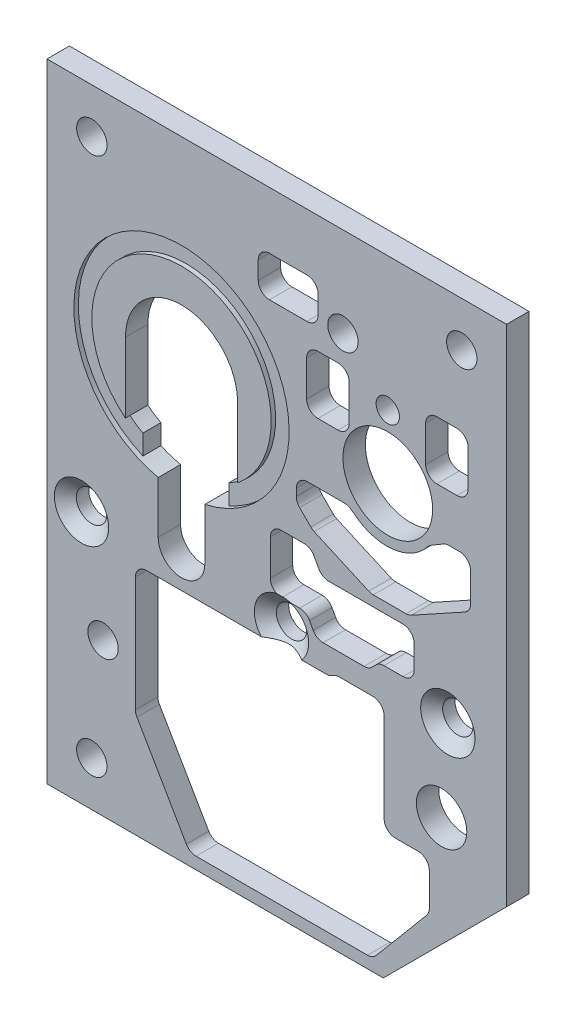
SolidWorks part; units mm, degrees
material "Acrylic (Medium-high impact)"
ref_plane "Front Plane" through (0, 0, 0) normal (0, 0, 1) x (1, 0, 0)
ref_plane "Top Plane" through (0, 0, 0) normal (0, 1, 0) x (1, 0, 0)
ref_plane "Right Plane" through (0, 0, 0) normal (1, 0, 0) x (0, 0, -1)
sketch "Sketch1" plane through (0, 0, 0) normal (0, 0, 1) x (1, 0, 0)
  line L5 (-65.0875, 0) -> (-65.0875, -88.9)
  line L6 (-65.0875, -88.9) -> (-17.4625, -88.9)
  line L7 (-17.4625, -88.9) -> (0, -71.4375)
  line L8 (0, -71.4375) -> (0, 0)
  line L9 (0, 0) -> (-65.0875, 0)
  line L10 (-65.0875, 0) -> (-65.0875, -88.9)
  line L11 (-65.0875, -88.9) -> (-17.4625, -88.9)
  line L12 (-17.4625, -88.9) -> (0, -71.4375)
  line L13 (0, -71.4375) -> (0, 0)
  line L14 (0, 0) -> (-65.0875, 0)
  dimension "D1" = 0
extrude "Boss-Extrude1" add sketch "Sketch1" against normal blind 3.175
hole_wizard "#6 Clearance Hole1" positions "Sketch3" profile "Sketch2" hole size "#6" standard "ANSI Inch" end condition through all
sketch "Sketch3" plane through (0, 0, 0) normal (0, 0, 1) x (1, 0, 0)
  point P0 (-58.7375, -6.35)
  point P3 (-6.35, -6.35)
  point P6 (-23.1775, -12.7)
  point P9 (-57.15, -67.31)
  point P12 (-58.7375, -82.55)
sketch "Sketch2" plane through (-58.7375, -6.35, 0) normal (1, 0, 0) x (0, -1, 0)
  line L0 (0, 0) -> (0, 3.175)
  line L1 (0, 3.175) -> (2.1526, 3.175)
  line L2 (2.1526, 3.175) -> (2.1526, 0)
  line L5 (2.1526, 0) -> (0, 0)
  line L11 (0, -6.35) -> (0, 107.95) construction
  dimension "Thru Hole Dia." = 4.3053
  dimension "Thru Hole Depth" = 3.175
sketch "Sketch4" plane through (0, 0, 0) normal (0, 0, 1) x (1, 0, 0)
  line L0 (-49.3395, -50.8) -> (-49.3395, -43.453) construction
  line L1 (-42.7355, -43.453) -> (-42.7355, -50.8) construction
  line L2 (-49.3395, -50.8) -> (-49.3395, -43.453)
  line L3 (-42.7355, -43.453) -> (-42.7355, -50.8)
  arc A0 (-42.7355, -43.453) -> (-49.3395, -43.453) centre (-46.0375, -28.575) ccw construction
  arc A1 (-49.3395, -50.8) -> (-42.7355, -50.8) centre (-46.0375, -50.8) ccw construction
  arc A2 (-42.7355, -43.453) -> (-49.3395, -43.453) centre (-46.0375, -28.575) ccw
  arc A3 (-49.3395, -50.8) -> (-42.7355, -50.8) centre (-46.0375, -50.8) ccw
extrude "Cut-Extrude1" cut sketch "Sketch4" against normal through all
sketch "Sketch5" plane through (0, 0, 0) normal (0, 0, 1) x (1, 0, 0)
  circle A0 centre (-16.8275, -27.94) radius 6.35
  circle A1 centre (-16.8275, -18.9484) radius 1.651
  dimension "D1" = 12.7
  dimension "D2" = 3.302
  dimension "D3" = 8.9916
extrude "Cut-Extrude2" cut sketch "Sketch5" against normal through all
hole_wizard "1/4 Clearance Hole1" positions "Sketch7" profile "Sketch6" hole size "1/4" standard "ANSI Inch" end condition through all
sketch "Sketch7" plane through (0, 0, 0) normal (0, 0, 1) x (1, 0, 0)
  point P0 (-9.2075, -65.0875)
sketch "Sketch6" plane through (-9.2075, -65.0875, 0) normal (1, 0, 0) x (0, -1, 0)
  line L0 (0, 0) -> (0, 3.175)
  line L1 (0, 3.175) -> (3.5712, 3.175)
  line L2 (3.5712, 3.175) -> (3.5712, 0)
  line L5 (3.5712, 0) -> (0, 0)
  line L11 (0, -6.35) -> (0, 107.95) construction
  dimension "Thru Hole Dia." = 7.1425
  dimension "Thru Hole Depth" = 3.175
sketch "Sketch8" plane through (0, 0, -3.175) normal (0, 0, -1) x (-1, 0, 0)
  line L0 (52.1335, -39.7163) -> (52.1335, -42.5427) construction
  line L1 (53.975, -28.575) -> (53.975, -38.4889) construction
  line L2 (38.1, -38.4889) -> (38.1, -28.575) construction
  line L3 (39.9415, -42.5427) -> (39.9415, -39.7163) construction
  line L4 (52.1335, -39.7163) -> (52.1335, -42.5427)
  line L5 (53.975, -28.575) -> (53.975, -38.4889)
  line L6 (38.1, -38.4889) -> (38.1, -28.575)
  line L7 (39.9415, -42.5427) -> (39.9415, -39.7163)
  arc A0 (52.1335, -39.7163) -> (53.975, -38.4889) centre (46.0375, -28.575) ccw construction
  arc A1 (53.975, -28.575) -> (38.1, -28.575) centre (46.0375, -28.575) ccw construction
  arc A2 (38.1, -38.4889) -> (39.9415, -39.7163) centre (46.0375, -28.575) ccw construction
  arc A3 (49.3395, -43.453) -> (42.7355, -43.453) centre (46.0375, -28.575) ccw construction
  arc A4 (52.1335, -39.7163) -> (53.975, -38.4889) centre (46.0375, -28.575) ccw
  arc A5 (53.975, -28.575) -> (38.1, -28.575) centre (46.0375, -28.575) ccw
  arc A6 (38.1, -38.4889) -> (39.9415, -39.7163) centre (46.0375, -28.575) ccw
  arc A7 (52.1335, -42.5427) -> (39.9415, -42.5427) centre (46.0375, -28.575) ccw
extrude "Boss-Extrude2" add sketch "Sketch8" against normal through all
sketch "Sketch9" plane through (0, 0, 0) normal (0, 0, 1) x (1, 0, 0)
  line L0 (-52.1335, -39.7163) -> (-52.1335, -42.5427) construction
  line L1 (-39.9415, -42.5427) -> (-39.9415, -39.7163) construction
  line L2 (-52.1335, -39.7163) -> (-52.1335, -42.5427)
  line L3 (-39.9415, -42.5427) -> (-39.9415, -39.7163)
  arc A0 (-42.7355, -43.453) -> (-49.3395, -43.453) centre (-46.0375, -28.575) ccw construction
  arc A1 (-53.975, -38.4889) -> (-52.1335, -39.7163) centre (-46.0375, -28.575) ccw construction
  arc A2 (-38.1, -38.4889) -> (-53.975, -38.4889) centre (-46.0375, -28.575) ccw construction
  arc A3 (-39.9415, -39.7163) -> (-38.1, -38.4889) centre (-46.0375, -28.575) ccw construction
  arc A4 (-39.9415, -42.5427) -> (-52.1335, -42.5427) centre (-46.0375, -28.575) ccw
  arc A5 (-53.975, -38.4889) -> (-52.1335, -39.7163) centre (-46.0375, -28.575) ccw
  arc A6 (-38.1, -38.4889) -> (-53.975, -38.4889) centre (-46.0375, -28.575) ccw
  arc A7 (-39.9415, -39.7163) -> (-38.1, -38.4889) centre (-46.0375, -28.575) ccw
extrude "Cut-Extrude3" cut sketch "Sketch9" against normal blind 0.635
hole_wizard "CSK for #6 Flat Head Machine Screw (100)1" positions "Sketch11" profile "Sketch10" countersink size "#6" standard "ANSI Inch" end condition through all
sketch "Sketch11" plane through (0, 0, 0) normal (0, 0, 1) x (1, 0, 0)
  point P1 (-31.877, -53.0919)
  point P5 (-60.198, -53.0919)
  point P8 (-8.321, -53.0919)
sketch "Sketch10" plane through (-31.877, -53.0919, 0) normal (1, 0, 0) x (0, -1, 0)
  line L0 (0, 0) -> (0, 3.175)
  line L1 (0, 3.175) -> (2.1526, 3.175)
  line L2 (2.1526, 3.175) -> (2.1526, 1.4209)
  line L3 (2.1526, 1.4209) -> (3.846, 0)
  line L5 (3.846, 0) -> (0, 0)
  line L6 (-2.1526, 1.4209) -> (-3.846, 0) construction
  line L11 (0, -6.35) -> (0, 107.95) construction
  dimension "Thru Hole Dia." = 4.3053
  dimension "Thru Hole Depth" = 3.175
  dimension "Near C'Sink Dia." = 7.692
  dimension "Near C'Sink Angle" = 100
sketch "Sketch13" plane through (0, 0, 0) normal (0, 0, 1) x (1, 0, 0)
  line L0 (-33.5834, -8.0877) -> (-28.2715, -8.0877)
  line L1 (-26.684, -9.6752) -> (-26.684, -12.1963)
  line L2 (-28.2715, -13.7838) -> (-33.5834, -13.7838)
  line L3 (-35.1709, -9.6752) -> (-35.1709, -12.1963)
  line L4 (-9.8743, -16.2715) -> (-7.0294, -16.2715)
  line L5 (-5.4419, -17.859) -> (-5.4419, -22.9231)
  line L6 (-7.0294, -24.5106) -> (-9.8743, -24.5106)
  line L7 (-11.4618, -22.9231) -> (-11.4618, -17.859)
  line L8 (-26.728, -16.6728) -> (-23.8831, -16.6728)
  line L9 (-22.2956, -18.2603) -> (-22.2956, -23.3243)
  line L10 (-23.8831, -24.9118) -> (-26.728, -24.9118)
  line L11 (-28.3155, -23.3243) -> (-28.3155, -18.2603)
  line L17 (-13.0908, -45.6924) -> (-13.0908, -48.9531)
  line L23 (-33.4611, -47.8684) -> (-33.4611, -42.8044)
  line L24 (-29.3162, -37.1302) -> (-27.7292, -38.7172)
  line L25 (-27.2516, -39.0452) -> (-19.5276, -42.4798)
  line L26 (-18.8826, -42.6167) -> (-14.2496, -42.6167)
  line L27 (-13.4825, -42.4191) -> (-5.915, -38.243)
  line L28 (-5.0945, -36.8531) -> (-5.0945, -32.7951)
  line L29 (-6.682, -31.2076) -> (-8.167, -31.2076)
  line L32 (-22.9356, -33.4058) -> (-28.1937, -33.4058)
  line L33 (-29.7812, -34.9933) -> (-29.7812, -36.0077)
  line L34 (-50.973, -55.6802) -> (-25.5623, -55.6802)
  line L37 (-15.7595, -70.8877) -> (-12.5337, -70.8876)
  line L38 (-10.9462, -72.4751) -> (-10.9462, -77.1078)
  line L39 (-11.3183, -78.129) -> (-18.4811, -86.653)
  line L40 (-19.6965, -87.2192) -> (-43.9811, -87.2192)
  line L41 (-45.3548, -86.4273) -> (-52.3467, -74.3556)
  line L42 (-52.5605, -73.56) -> (-52.5605, -57.2677)
  line L43 (-14.6783, -44.1049) -> (-25.206, -44.1049)
  line L44 (-26.5981, -43.2804) -> (-27.2773, -42.0413)
  line L45 (-28.6694, -41.2169) -> (-31.8736, -41.2169)
  line L48 (-25.9975, -52.0435) -> (-20.1851, -52.0435)
  line L49 (-19.0626, -51.5785) -> (-18.4896, -51.0056)
  line L50 (-17.3671, -50.5406) -> (-14.6783, -50.5406)
  line L51 (-27.3896, -51.219) -> (-27.9041, -50.2804)
  line L52 (-29.2962, -49.4559) -> (-31.8736, -49.4559)
  line L54 (-24.662, -55.4002) -> (-24.6221, -55.3728)
  line L55 (-23.7218, -55.0928) -> (-18.9345, -55.0928)
  line L57 (-17.347, -56.6803) -> (-17.347, -69.3002)
  line L58 (-8.9781, -31.4305) -> (-10.7271, -32.4701)
  arc A0 (-28.2715, -8.0877) -> (-26.684, -9.6752) centre (-28.2715, -9.6752) cw
  arc A1 (-26.684, -12.1963) -> (-28.2715, -13.7838) centre (-28.2715, -12.1963) cw
  arc A2 (-33.5834, -13.7838) -> (-35.1709, -12.1963) centre (-33.5834, -12.1963) cw
  arc A3 (-33.5834, -8.0877) -> (-35.1709, -9.6752) centre (-33.5834, -9.6752) ccw
  arc A4 (-5.4419, -22.9231) -> (-7.0294, -24.5106) centre (-7.0294, -22.9231) cw
  arc A5 (-9.8743, -24.5106) -> (-11.4618, -22.9231) centre (-9.8743, -22.9231) cw
  arc A6 (-9.8743, -16.2715) -> (-11.4618, -17.859) centre (-9.8743, -17.859) ccw
  arc A7 (-7.0294, -16.2715) -> (-5.4419, -17.859) centre (-7.0294, -17.859) cw
  arc A8 (-22.2956, -23.3243) -> (-23.8831, -24.9118) centre (-23.8831, -23.3243) cw
  arc A9 (-26.728, -24.9118) -> (-28.3155, -23.3243) centre (-26.728, -23.3243) cw
  arc A10 (-26.728, -16.6728) -> (-28.3155, -18.2603) centre (-26.728, -18.2603) ccw
  arc A11 (-23.8831, -16.6728) -> (-22.2956, -18.2603) centre (-23.8831, -18.2603) cw
  arc A16 (-13.0908, -48.9531) -> (-14.6783, -50.5406) centre (-14.6783, -48.9531) cw
  arc A19 (-14.6783, -44.1049) -> (-13.0908, -45.6924) centre (-14.6783, -45.6924) cw
  arc A21 (-31.8736, -49.4559) -> (-33.4611, -47.8684) centre (-31.8736, -47.8684) cw
  arc A22 (-31.8736, -41.2169) -> (-33.4611, -42.8044) centre (-31.8736, -42.8044) ccw
  arc A24 (-19.5276, -42.4798) -> (-18.8826, -42.6167) centre (-18.8826, -41.0292) ccw
  arc A25 (-14.2496, -42.6167) -> (-13.4825, -42.4191) centre (-14.2496, -41.0292) ccw
  arc A26 (-5.915, -38.243) -> (-5.0945, -36.8531) centre (-6.682, -36.8531) ccw
  arc A27 (-5.0945, -32.7951) -> (-6.682, -31.2076) centre (-6.682, -32.7951) ccw
  arc A31 (-27.7292, -38.7172) -> (-27.2516, -39.0452) centre (-26.6066, -37.5947) ccw
  arc A32 (-29.3162, -37.1302) -> (-29.7812, -36.0077) centre (-28.1937, -36.0077) cw
  arc A33 (-28.1937, -33.4058) -> (-29.7812, -34.9933) centre (-28.1937, -34.9933) ccw
  arc A37 (-12.5337, -70.8876) -> (-10.9462, -72.4751) centre (-12.5337, -72.4751) cw
  arc A38 (-10.9462, -77.1078) -> (-11.3183, -78.129) centre (-12.5337, -77.1078) cw
  arc A39 (-18.4811, -86.653) -> (-19.6965, -87.2192) centre (-19.6965, -85.6317) cw
  arc A40 (-43.9811, -87.2192) -> (-45.3548, -86.4273) centre (-43.9811, -85.6317) cw
  arc A41 (-52.3467, -74.3556) -> (-52.5605, -73.56) centre (-50.973, -73.56) cw
  arc A42 (-50.973, -55.6802) -> (-52.5605, -57.2677) centre (-50.973, -57.2677) ccw
  arc A43 (-27.2773, -42.0413) -> (-28.6694, -41.2169) centre (-28.6694, -42.8044) ccw
  arc A44 (-25.206, -44.1049) -> (-26.5981, -43.2804) centre (-25.206, -42.5174) cw
  arc A45 (-18.4896, -51.0056) -> (-17.3671, -50.5406) centre (-17.3671, -52.1281) cw
  arc A46 (-20.1851, -52.0435) -> (-19.0626, -51.5785) centre (-20.1851, -50.456) ccw
  arc A47 (-27.3896, -51.219) -> (-25.9975, -52.0435) centre (-25.9975, -50.456) ccw
  arc A48 (-27.9041, -50.2804) -> (-29.2962, -49.4559) centre (-29.2962, -51.0434) ccw
  arc A49 (-15.7595, -70.8877) -> (-17.347, -69.3002) centre (-15.7595, -69.3002) cw
  arc A50 (-18.9345, -55.0928) -> (-17.347, -56.6803) centre (-18.9345, -56.6803) cw
  arc A51 (-24.6221, -55.3728) -> (-23.7218, -55.0928) centre (-23.7218, -56.6803) cw
  arc A52 (-24.662, -55.4002) -> (-25.5623, -55.6802) centre (-25.5623, -54.0927) cw
  arc A53 (-11.1669, -32.8573) -> (-21.8769, -33.8104) centre (-16.9676, -28.3255) cw
  arc A54 (-22.9356, -33.4058) -> (-21.8769, -33.8104) centre (-22.9356, -34.9933) cw
  arc A55 (-11.1669, -32.8573) -> (-10.7271, -32.4701) centre (-9.916, -33.8347) cw
  arc A56 (-8.167, -31.2076) -> (-8.9781, -31.4305) centre (-8.167, -32.7951) ccw
  dimension "D1" = 1.5875
  dimension "D2" = 1.5875
  dimension "D3" = 1.5875
  dimension "D4" = 1.5875
  dimension "D5" = 1.5875
  dimension "D6" = 1.5875
  dimension "D7" = 1.5875
  dimension "D8" = 1.5875
extrude "Backlighting Holes" cut sketch "Sketch13" against normal through all
